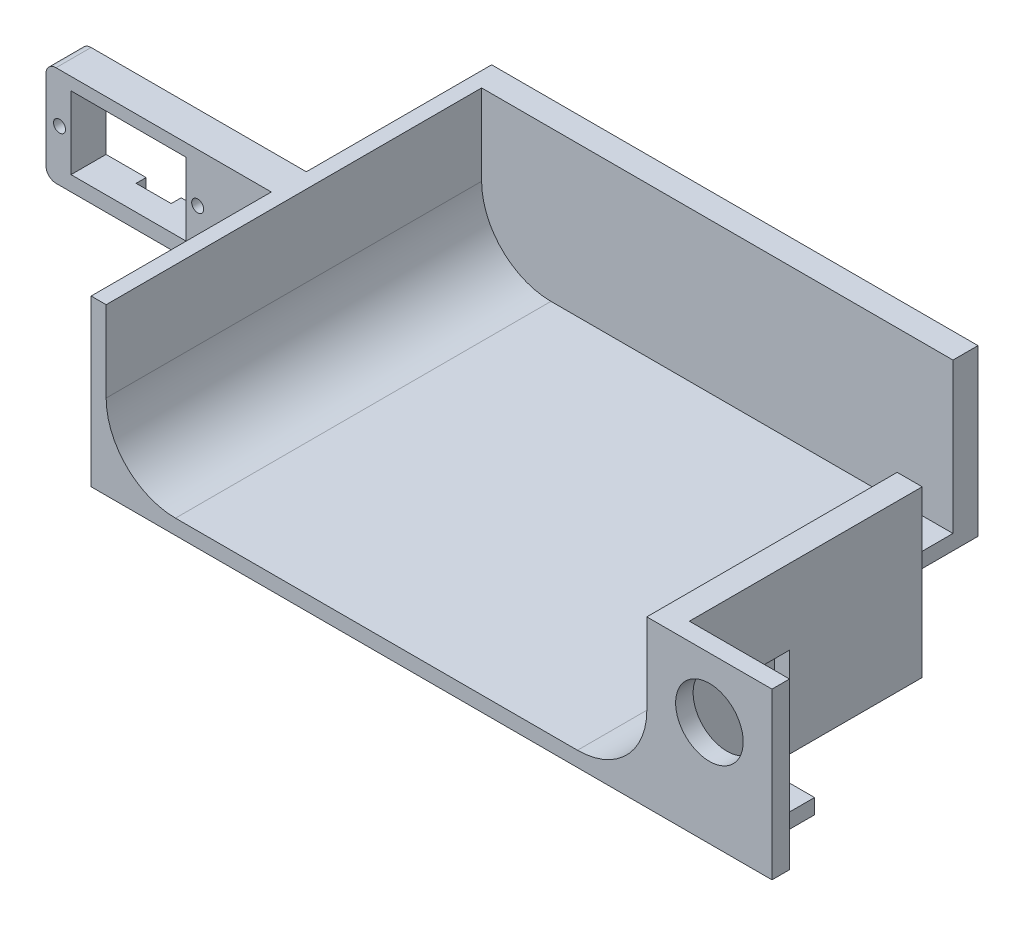
SolidWorks part; units mm, degrees
ref_plane "Plan de face" through (0, 0, 0) normal (0, 0, 1) x (1, 0, 0)
ref_plane "Plan de dessus" through (0, 0, 0) normal (0, 1, 0) x (1, 0, 0)
ref_plane "Plan de droite" through (0, 0, 0) normal (1, 0, 0) x (0, 0, -1)
sketch "Esquisse1" plane through (0, 0, 0) normal (0, 1, 0) x (1, 0, 0)
  line L1 (0, 0) -> (138, 0)
  line L2 (0, 0) -> (0, 75)
  line L3 (0, 75) -> (138, 75)
  line L4 (138, 0) -> (138, 75)
  dimension "D1" = 138
  dimension "D2" = 75
extrude "Boss.-Extru.1" add sketch "Esquisse1" along normal blind 3
sketch "Esquisse2" plane through (0, 3, 0) normal (0, 1, 0) x (1, 0, 0)
  line L0 (0, 0) -> (138, 0) construction
  line L1 (0, 75) -> (5, 75)
  line L2 (0, 75) -> (0, 0)
  line L3 (0, 0) -> (5, 0)
  line L4 (5, 75) -> (5, 0)
  line L6 (138, 75) -> (113, 75)
  line L7 (138, 75) -> (138, 0)
  line L8 (138, 0) -> (113, 0)
  line L9 (113, 75) -> (113, 0)
  dimension "D1" = 25
  dimension "D2" = 5
extrude "Boss.-Extru.2" add sketch "Esquisse2" along normal blind 30
fillet "Congé1" radius 13.85 2 edges at (113, 3, -37.5) (5, 3, -37.5)
sketch "Esquisse3" plane through (0, 0, -75) normal (0, 0, -1) x (-1, 0, 0)
  line L1 (-138, 0) -> (0, 0)
  line L2 (-138, 0) -> (-138, 33)
  line L3 (-138, 33) -> (0, 33)
  line L4 (0, 0) -> (0, 33)
extrude "Boss.-Extru.3" add sketch "Esquisse3" along normal blind 5
sketch "Esquisse4" plane through (0, 0, 0) normal (-1, 0, 0) x (0, 0, 1)
  line L1 (0, 33) -> (-25, 33)
  line L2 (0, 33) -> (0, 13)
  line L3 (0, 13) -> (-25, 13)
  line L4 (-25, 33) -> (-25, 13)
  dimension "D1" = 25
  dimension "D2" = 20
extrude "Enlèv. mat.-Extru.1" [suppressed] cut sketch "Esquisse4" against normal blind 6
sketch "Esquisse5" plane through (0, 33, 0) normal (0, 1, 0) x (1, 0, 0)
  line L0 (113, 75) -> (113, 0) construction
  line L1 (138, 80) -> (118, 80)
  line L2 (138, 80) -> (138, 3.5)
  line L3 (138, 3.5) -> (118, 3.5)
  line L4 (118, 80) -> (118, 3.5)
  line L5 (113, 0) -> (138, 0) construction
  dimension "D1" = 5
  dimension "D2" = 3.5
extrude "Enlèv. mat.-Extru.2" cut sketch "Esquisse5" against normal blind 30
sketch "Esquisse6" plane through (0, 0, 0) normal (0, 0, 1) x (1, 0, 0)
  line L0 (113, 33) -> (138, 33) construction
  line L3 (138, 33) -> (138, 0) construction
  circle A0 centre (125.5, 21) radius 6.25
  dimension "D3" = 12.5
  dimension "D1" = 12
  dimension "D2" = 12.5
extrude "Enlèv. mat.-Extru.3" cut sketch "Esquisse6" against normal up to surface (3.5 mm away) up to face at (128, 18, -3.5)
sketch "Esquisse7" plane through (0, 0, -80) normal (0, 0, -1) x (-1, 0, 0)
  line L1 (-138, 0) -> (-118, 0)
  line L2 (-138, 0) -> (-138, 3)
  line L3 (-138, 3) -> (-118, 3)
  line L4 (-118, 0) -> (-118, 3)
extrude "Enlèv. mat.-Extru.4" cut sketch "Esquisse7" against normal blind 30
sketch "Esquisse8" plane through (0, 33, 0) normal (0, 1, 0) x (1, 0, 0)
  line L0 (99.15, 0) -> (99.15, 75) construction
  line L1 (118, 80) -> (99.15, 80)
  line L2 (118, 80) -> (118, 50)
  line L3 (118, 50) -> (99.15, 50)
  line L4 (99.15, 80) -> (99.15, 50)
  dimension "D1" = 30
extrude "Enlèv. mat.-Extru.5" cut sketch "Esquisse8" against normal up to surface (33 mm away) up to face at (85.3333, 0, -43.3333)
sketch "Esquisse10" plane through (118, 0, 0) normal (1, 0, 0) x (0, 0, -1)
  line L0 (50, 3) -> (3.5, 3) construction
  line L1 (15.5, 3) -> (23.5, 3)
  line L2 (15.5, 3) -> (15.5, 18)
  line L3 (15.5, 18) -> (23.5, 18)
  line L4 (23.5, 3) -> (23.5, 18)
  dimension "D1" = 12
  dimension "D2" = 8
  dimension "D3" = 15
extrude "Enlèv. mat.-Extru.6" cut sketch "Esquisse10" against normal offset from surface (3 mm away) 2 up to face at (113, 24.925, -25)
sketch "Esquisse11" plane through (0, 3, 0) normal (0, 1, 0) x (1, 0, 0)
  line L1 (115, 23.5) -> (118, 23.5)
  line L2 (115, 23.5) -> (115, 15.5)
  line L3 (115, 15.5) -> (131, 15.5)
  line L8 (138, 3.5) -> (131, 3.5)
  line L9 (131, 15.5) -> (131, 3.5)
  line L10 (138, 50) -> (138, 3.5)
  line L11 (118, 50) -> (138, 50)
  line L12 (118, 50) -> (118, 23.5)
  dimension "D1" = 12
  dimension "D2" = 7
  dimension "D3" = 20
extrude "Enlèv. mat.-Extru.7" cut sketch "Esquisse11" against normal up to surface (3 mm away) up to face at (79.05, 0, -43.3333)
sketch "Esquisse12" plane through (0, 0, 0) normal (-1, 0, 0) x (0, 0, 1)
  line L1 (-80, 33) -> (0, 33)
  line L2 (-80, 33) -> (-80, 0)
  line L3 (-80, 0) -> (0, 0)
  line L4 (0, 33) -> (0, 0)
extrude "Enlèv. mat.-Extru.8" cut sketch "Esquisse12" against normal blind 2
sketch "Esquisse13" plane through (0, 0, 0) normal (0, 0, 1) x (1, 0, 0)
  line L0 (37, 0) -> (44.5969, -20)
  line L1 (2, 0) -> (138, 0) construction
  line L2 (44.5969, -20) -> (71.5969, -20)
  line L3 (71.5969, -20) -> (78, 0)
  line L4 (78, 0) -> (37, 0)
  line L7 (113, 33) -> (113, 16.85) construction
  dimension "D1" = 35
  dimension "D2" = 27
  dimension "D3" = 35
  dimension "D4" = 20
  dimension "D5" = 21
extrude "Boss.-Extru.4" [suppressed] add sketch "Esquisse13" against normal blind 7
sketch "Esquisse14" [suppressed] plane through (0, 0, 0) normal (0, 0, 1) x (1, 0, 0)
  line L0 (44.5969, -20) -> (71.5969, -20) construction
  line L1 (46.5, -2.5) -> (69.5, -2.5)
  line L2 (46.5, -2.5) -> (46.5, -17)
  line L3 (46.5, -17) -> (69.5, -17)
  line L4 (69.5, -2.5) -> (69.5, -17)
  dimension "D1" = 23
  dimension "D2" = 9.5
  dimension "D3" = 3
  dimension "D4" = 14.5
extrude "Enlèv. mat.-Extru.9" [suppressed] cut sketch "Esquisse14" against normal up to surface (7 mm away) up to face at (131.75, 21, 0)
fillet "Congé2" [suppressed] radius 10
sketch "Esquisse15" plane through (2, 0, 0) normal (-1, 0, 0) x (0, 0, 1)
  line L0 (0, 33) -> (-80, 33) construction
  line L1 (-42.9875, 33) -> (-35.9875, 33)
  line L2 (-42.9875, 33) -> (-42.9875, 13)
  line L3 (-42.9875, 13) -> (-35.9875, 13)
  line L4 (-35.9875, 33) -> (-35.9875, 13)
  dimension "D1" = 20
  dimension "D2" = 7
extrude "Boss.-Extru.5" add sketch "Esquisse15" along normal blind 45
sketch "Esquisse16" plane through (0, 0, -35.9875) normal (0, 0, 1) x (1, 0, 0)
  line L0 (-20.5, 33) -> (-20.5, 13) construction
  line L1 (-43, 33) -> (2, 33) construction
  line L2 (-43, 13) -> (2, 13) construction
  line L3 (-43, 23) -> (2, 23) construction
  line L4 (-43, 13) -> (-43, 33) construction
  line L5 (2, 13) -> (2, 33) construction
  line L7 (-38, 30.5) -> (-15, 30.5)
  line L8 (-38, 30.5) -> (-38, 16)
  line L9 (-38, 16) -> (-15, 16)
  line L10 (-15, 30.5) -> (-15, 16)
  dimension "D1" = 23
  dimension "D2" = 14.5
  dimension "D3" = 2.5
  dimension "D4" = 5
extrude "Enlèv. mat.-Extru.10" cut sketch "Esquisse16" against normal up to surface (7 mm away) up to face at (-20.5, 23, -42.9875)
fillet "Congé3" radius 20 1 edges at (2, 13, -39.4875)
fillet "Congé4" radius 2 2 edges at (-43, 33, -39.4875) (-43, 13, -39.4875)
sketch "Esquisse18" plane through (0, 0, -42.9875) normal (0, 0, -1) x (-1, 0, 0)
  line L0 (15, 16) -> (38, 16) construction
  line L1 (23, 16) -> (30, 16)
  line L2 (23, 16) -> (23, 13)
  line L3 (23, 13) -> (30, 13)
  line L4 (30, 16) -> (30, 13)
  line L6 (41, 13) -> (16.735, 13) construction
  dimension "D1" = 8
  dimension "D2" = 8
extrude "Enlèv. mat.-Extru.11" cut sketch "Esquisse18" against normal blind 2
sketch "Esquisse20" plane through (0, 0, -42.9875) normal (0, 0, -1) x (-1, 0, 0)
  line L0 (38, 30.5) -> (15, 30.5) construction
  line L1 (10.4, 25.9) -> (15, 25.9)
  line L2 (10.4, 25.9) -> (10.4, 20.6)
  line L3 (10.4, 20.6) -> (15, 20.6)
  line L4 (15, 25.9) -> (15, 20.6)
  line L5 (38, 25.9) -> (42.6, 25.9)
  line L6 (38, 25.9) -> (38, 20.6)
  line L7 (38, 20.6) -> (42.6, 20.6)
  line L8 (42.6, 25.9) -> (42.6, 20.6)
  line L9 (15, 16) -> (23, 16) construction
  line L10 (15, 30.5) -> (15, 16) construction
  line L11 (38, 16) -> (38, 30.5) construction
  line L12 (30, 16) -> (38, 16) construction
  dimension "D1" = 4.6
  dimension "D2" = 4.6
  dimension "D3" = 4.6
  dimension "D4" = 4.6
  dimension "D5" = 4.6
  dimension "D6" = 4.6
sketch "Esquisse21" plane through (0, 0, -42.9875) normal (0, 0, -1) x (-1, 0, 0)
  line L0 (15, 25.9) -> (15, 20.6) construction
  line L1 (10.4, 25.9) -> (10.4, 20.6) construction
  line L2 (10.4, 23.25) -> (15, 23.25) construction
  line L3 (15, 23.25) -> (42.6, 23.25) construction
  line L4 (42.6, 25.9) -> (42.6, 20.6) construction
  circle A0 centre (12.7, 23.25) radius 1
  circle A1 centre (40.3, 23.25) radius 1
  point P10 (0, 0)
  point P14 (0, 0)
  point P15 (0, 0)
  dimension "D1" = 2
  dimension "D3" = 2
  dimension "D2" = 2.3
extrude "Enlèv. mat.-Extru.12" cut sketch "Esquisse21" against normal up to surface (7 mm away) up to face at (-26.5, 23.25, -35.9875)
hole_wizard "Dégagement M21" positions "Esquisse22" profile "Esquisse23" hole size "M2" standard "ISO"
sketch "Esquisse22" plane through (0, 0, -42.9875) normal (0, 0, -1) x (-1, 0, 0)
  point P0 (40.3, 23.25)
  point P3 (12.7, 23.25)
sketch "Esquisse23" plane through (-40.3, 23.25, -42.9875) normal (1, 0, 0) x (0, 1, 0)
  line L0 (0, 0) -> (0, 10.721)
  line L1 (0, 10.721) -> (1.2, 10)
  line L2 (1.2, 10) -> (1.2, 0)
  line L5 (1.2, 0) -> (0, 0)
  line L10 (0, 10.721) -> (-1.2, 10) construction
  line L11 (0, -6.35) -> (0, 107.95) construction
  dimension "Diamètre du perçage" = 2.4
  dimension "Profondeur du perçage" = 10
  dimension "Angle de pointe" = 118
hole_wizard "Dégagement M121" positions "Esquisse24" profile "Esquisse25" hole size "M12" standard "ISO"
sketch "Esquisse24" plane through (0, 0, 0) normal (0, 0, 1) x (1, 0, 0)
  point P0 (125.5, 21)
sketch "Esquisse25" plane through (125.5, 21, 0) normal (1, 0, 0) x (0, -1, 0)
  line L0 (0, 0) -> (0, 14.0558)
  line L1 (0, 14.0558) -> (6.75, 10)
  line L2 (6.75, 10) -> (6.75, 0)
  line L5 (6.75, 0) -> (0, 0)
  line L10 (0, 14.0558) -> (-6.75, 10) construction
  line L11 (0, -6.35) -> (0, 107.95) construction
  dimension "Diamètre du perçage" = 13.5
  dimension "Profondeur du perçage" = 10
  dimension "Angle de pointe" = 118
